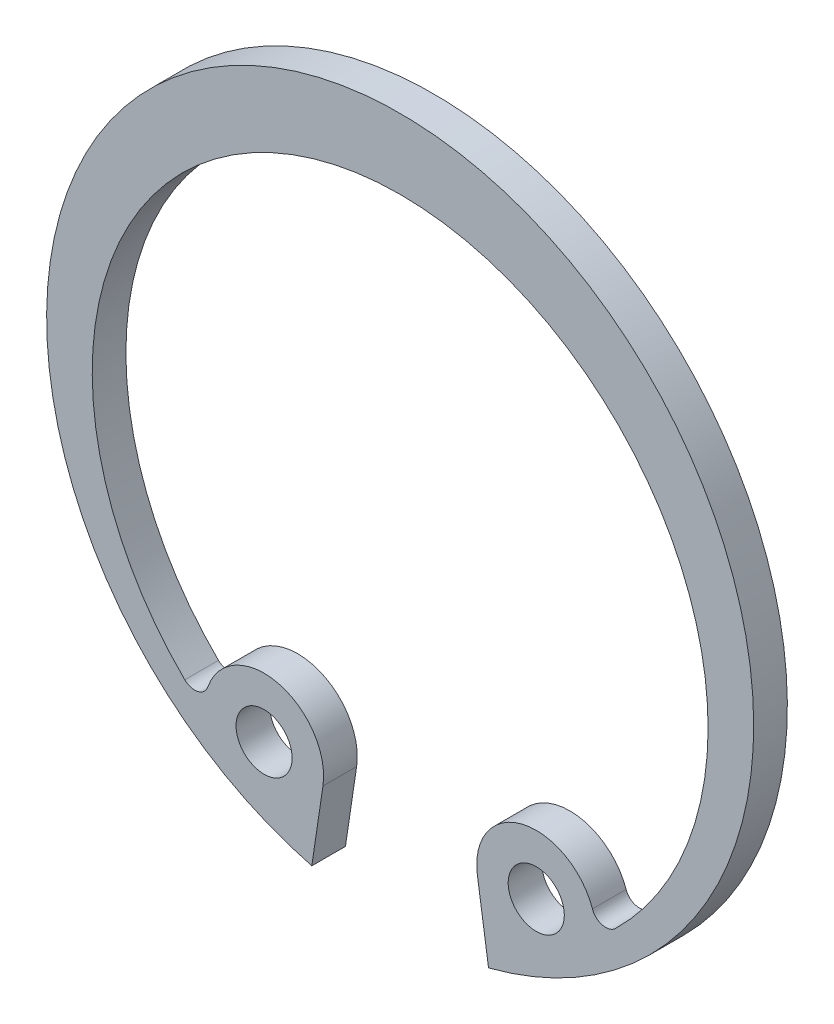
SolidWorks part; units mm, degrees
ref_plane "Front Plane" through (0, 0, 0) normal (0, 0, 1) x (1, 0, 0)
ref_plane "Top Plane" through (0, 0, 0) normal (0, 1, 0) x (1, 0, 0)
ref_plane "Right Plane" through (0, 0, 0) normal (1, 0, 0) x (0, 0, -1)
sketch "Sketch1" plane through (0, 0, 0) normal (0, 0, 1) x (1, 0, 0)
  line L0 (0, 0) -> (0, 12.6) construction
  line L1 (-2.7521, -9.5374) -> (-3.15, -12.1999)
  line L2 (2.7521, -9.5374) -> (3.15, -12.1999)
  line L3 (3.8628, -7.3463) -> (5.864, -11.1523) construction
  arc A0 (3.15, -12.1999) -> (-3.15, -12.1999) centre (0, 0) ccw
  arc A1 (-7.6753, -8.7198) -> (-6.8534, -8.5267) centre (-7.3256, -8.3624) ccw
  circle A2 centre (-4.85, -9.2238) radius 1
  circle A3 centre (4.85, -9.2238) radius 1
  circle A4 centre (0, 0) radius 7.5 construction
  arc A6 (-2.7521, -9.5374) -> (-6.8534, -8.5267) centre (-4.85, -9.2238) ccw
  arc A7 (6.8534, -8.5267) -> (2.7521, -9.5374) centre (4.85, -9.2238) ccw
  arc A8 (7.6753, -8.7198) -> (-7.6753, -8.7198) centre (0, -0.875) ccw
  arc A9 (7.6753, -8.7198) -> (6.8534, -8.5267) centre (7.3256, -8.3624) cw
  point P13 (0, 10.1)
  dimension "RIC_D2_s" = 25.2
  dimension "RIC_D0_s" = 2
  dimension "RIC_D4_s" = 21.95
  dimension "D1" = 0.5
  dimension "RIC_D5_s" = 15
  dimension "RIC_MSM_2" = 9.7
  dimension "D2" = 17
  dimension "RIC_MSM_1" = 6.3
  dimension "RIC_B_s" = 2.5
  dimension "RIC_A_s" = 4.3
extrude "Boss-Extrude1" add sketch "Sketch1" along normal blind 1.2
equation "\"RIC_D4_s@Sketch1\"=\"RIC_D2_s@Sketch1\"-1.3*\"RIC_B_s@Sketch1\""
